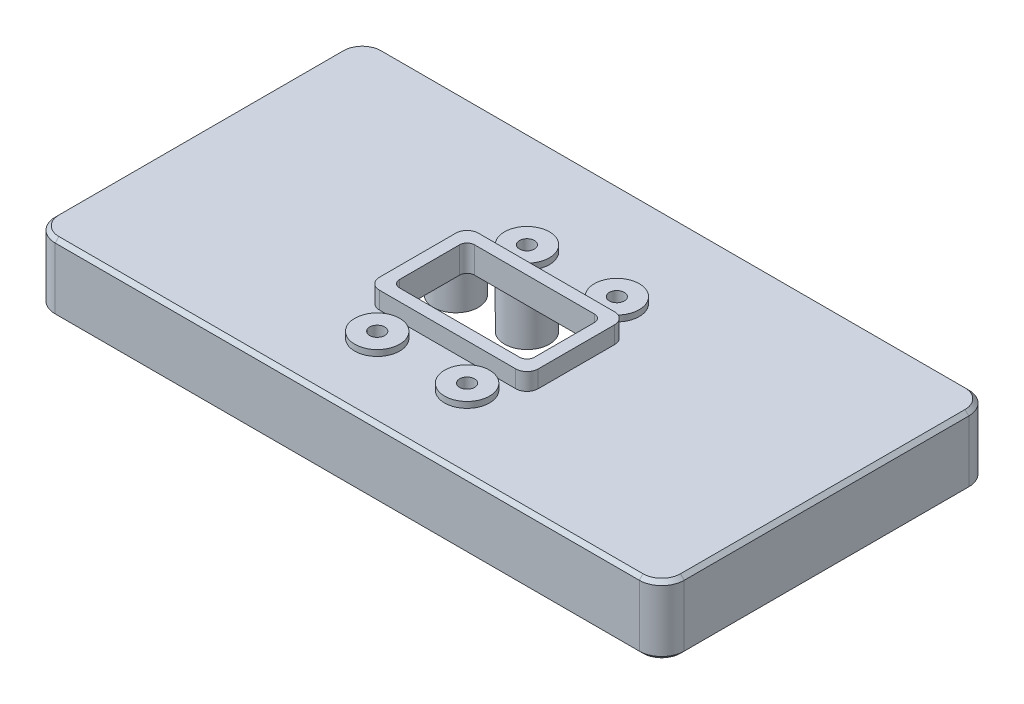
SolidWorks part; units mm, degrees
ref_plane "Front Plane" through (0, 0, 0) normal (0, 0, 1) x (1, 0, 0)
ref_plane "Top Plane" through (0, 0, 0) normal (0, 1, 0) x (1, 0, 0)
ref_plane "Right Plane" through (0, 0, 0) normal (1, 0, 0) x (0, 0, -1)
sketch "Sketch1" plane through (0, 0, 0) normal (0, 1, 0) x (1, 0, 0)
  line L0 (-39, -36) -> (39, -36)
  line L1 (42, -39) -> (42, -77)
  line L2 (39, -80) -> (-39, -80)
  line L3 (-42, -77) -> (-42, -39)
  arc A0 (-42, -39) -> (-39, -36) centre (-39, -39) cw
  arc A1 (39, -36) -> (42, -39) centre (39, -39) cw
  arc A2 (42, -77) -> (39, -80) centre (39, -77) cw
  arc A3 (-39, -80) -> (-42, -77) centre (-39, -77) cw
extrude "Boss-Extrude1" add sketch "Sketch1" along normal blind 9.2 from offset 50
chamfer "Chamfer1" distance 0.5 angle 45 8 edges at (0, 50, 36) (-41.1213, 50, 36.8787) (41.1213, 50, 36.8787) (-42, 50, 58) (42, 50, 58) (-41.1213, 50, 79.1213) (41.1213, 50, 79.1213) (0, 50, 80)
chamfer "Chamfer2" distance 0.5 angle 45 8 edges at (0, 59.2, 36) (-41.1213, 59.2, 36.8787) (41.1213, 59.2, 36.8787) (-42, 59.2, 58) (42, 59.2, 58) (-41.1213, 59.2, 79.1213) (41.1213, 59.2, 79.1213) (0, 59.2, 80)
sketch "Sketch2" plane through (0, 0, 0) normal (0, 1, 0) x (1, 0, 0)
  line L0 (-39, -37.6) -> (39, -37.6)
  line L1 (40.4, -39) -> (40.4, -77)
  line L2 (39, -78.4) -> (-39, -78.4)
  line L3 (-40.4, -77) -> (-40.4, -39)
  arc A0 (-40.4, -39) -> (-39, -37.6) centre (-39, -39) cw
  arc A1 (39, -37.6) -> (40.4, -39) centre (39, -39) cw
  arc A2 (40.4, -77) -> (39, -78.4) centre (39, -77) cw
  arc A3 (-39, -78.4) -> (-40.4, -77) centre (-39, -77) cw
extrude "Boss-Extrude2" add sketch "Sketch2" along normal blind 9 from offset 49 separate body
combine bodies "Combine1" operation type subtract main body 101 bodies to subtract 102
sketch "Sketch3" plane through (0, 0, 0) normal (0, 1, 0) x (1, 0, 0)
  circle A0 centre (-15, -50.5) radius 3
extrude "Boss-Extrude3" add sketch "Sketch3" along normal blind 8.01 from offset 50
sketch "Sketch4" plane through (0, 0, 0) normal (0, 1, 0) x (1, 0, 0)
  circle A0 centre (-15, -50.5) radius 1
extrude "Boss-Extrude4" add sketch "Sketch4" along normal blind 9.4 from offset 49 separate body
combine bodies "Combine2" operation type subtract main body 104 bodies to subtract 105
sketch "Sketch5" plane through (0, 0, 0) normal (0, 1, 0) x (1, 0, 0)
  circle A0 centre (-15, -69.5) radius 3
extrude "Boss-Extrude5" add sketch "Sketch5" along normal blind 8.01 from offset 50
sketch "Sketch6" plane through (0, 0, 0) normal (0, 1, 0) x (1, 0, 0)
  circle A0 centre (-15, -69.5) radius 1
extrude "Boss-Extrude6" add sketch "Sketch6" along normal blind 9.4 from offset 49 separate body
combine bodies "Combine3" operation type subtract main body 107 bodies to subtract 108
sketch "Sketch7" plane through (0, 0, 0) normal (0, 1, 0) x (1, 0, 0)
  circle A0 centre (15, -50.5) radius 3
extrude "Boss-Extrude7" add sketch "Sketch7" along normal blind 8.01 from offset 50
sketch "Sketch8" plane through (0, 0, 0) normal (0, 1, 0) x (1, 0, 0)
  circle A0 centre (15, -50.5) radius 1
extrude "Boss-Extrude8" add sketch "Sketch8" along normal blind 9.4 from offset 49 separate body
combine bodies "Combine4" operation type subtract main body 110 bodies to subtract 111
sketch "Sketch9" plane through (0, 0, 0) normal (0, 1, 0) x (1, 0, 0)
  circle A0 centre (15, -69.5) radius 3
extrude "Boss-Extrude9" add sketch "Sketch9" along normal blind 8.01 from offset 50
sketch "Sketch10" plane through (0, 0, 0) normal (0, 1, 0) x (1, 0, 0)
  circle A0 centre (15, -69.5) radius 1
extrude "Boss-Extrude10" add sketch "Sketch10" along normal blind 9.4 from offset 49 separate body
combine bodies "Combine5" operation type subtract main body 113 bodies to subtract 114
sketch "Sketch11" plane through (0, 0, 0) normal (0, 1, 0) x (1, 0, 0)
  circle A0 centre (-6, -50) radius 3
extrude "Boss-Extrude11" add sketch "Sketch11" along normal blind 10 from offset 50
sketch "Sketch12" plane through (0, 0, 0) normal (0, 1, 0) x (1, 0, 0)
  circle A0 centre (-6, -50) radius 1
extrude "Boss-Extrude12" add sketch "Sketch12" along normal blind 9.5 from offset 51.5 separate body
combine bodies "Combine6" operation type subtract main body 116 bodies to subtract 117
sketch "Sketch13" plane through (0, 0, 0) normal (0, 1, 0) x (1, 0, 0)
  circle A0 centre (-6, -70) radius 3
extrude "Boss-Extrude13" add sketch "Sketch13" along normal blind 10 from offset 50
sketch "Sketch14" plane through (0, 0, 0) normal (0, 1, 0) x (1, 0, 0)
  circle A0 centre (-6, -70) radius 1
extrude "Boss-Extrude14" add sketch "Sketch14" along normal blind 9.5 from offset 51.5 separate body
combine bodies "Combine7" operation type subtract main body 119 bodies to subtract 120
sketch "Sketch15" plane through (0, 0, 0) normal (0, 1, 0) x (1, 0, 0)
  circle A0 centre (6, -50) radius 3
extrude "Boss-Extrude15" add sketch "Sketch15" along normal blind 10 from offset 50
sketch "Sketch16" plane through (0, 0, 0) normal (0, 1, 0) x (1, 0, 0)
  circle A0 centre (6, -50) radius 1
extrude "Boss-Extrude16" add sketch "Sketch16" along normal blind 9.5 from offset 51.5 separate body
combine bodies "Combine8" operation type subtract main body 122 bodies to subtract 123
sketch "Sketch17" plane through (0, 0, 0) normal (0, 1, 0) x (1, 0, 0)
  circle A0 centre (6, -70) radius 3
extrude "Boss-Extrude17" add sketch "Sketch17" along normal blind 10 from offset 50
sketch "Sketch18" plane through (0, 0, 0) normal (0, 1, 0) x (1, 0, 0)
  circle A0 centre (6, -70) radius 1
extrude "Boss-Extrude18" add sketch "Sketch18" along normal blind 9.5 from offset 51.5 separate body
combine bodies "Combine9" operation type subtract main body 125 bodies to subtract 126
sketch "Sketch19" plane through (0, 0, 0) normal (0, 1, 0) x (1, 0, 0)
  line L0 (-38.99, -37.59) -> (38.99, -37.59)
  line L1 (40.39, -38.99) -> (40.39, -77.01)
  line L2 (38.99, -78.41) -> (-38.99, -78.41)
  line L3 (-40.39, -77.01) -> (-40.39, -38.99)
  line L4 (-33.6, -39.6) -> (33.6, -39.6)
  line L5 (34.6, -40.6) -> (34.6, -71.6)
  line L6 (33.6, -72.6) -> (-33.6, -72.6)
  line L7 (-34.6, -71.6) -> (-34.6, -40.6)
  arc A0 (-40.39, -38.99) -> (-38.99, -37.59) centre (-38.99, -38.99) cw
  arc A1 (38.99, -37.59) -> (40.39, -38.99) centre (38.99, -38.99) cw
  arc A2 (40.39, -77.01) -> (38.99, -78.41) centre (38.99, -77.01) cw
  arc A3 (-38.99, -78.41) -> (-40.39, -77.01) centre (-38.99, -77.01) cw
  arc A4 (-34.6, -40.6) -> (-33.6, -39.6) centre (-33.6, -40.6) cw
  arc A5 (33.6, -39.6) -> (34.6, -40.6) centre (33.6, -40.6) cw
  arc A6 (34.6, -71.6) -> (33.6, -72.6) centre (33.6, -71.6) cw
  arc A7 (-33.6, -72.6) -> (-34.6, -71.6) centre (-33.6, -71.6) cw
extrude "Boss-Extrude19" add sketch "Sketch19" along normal blind 1.2 from offset 50
sketch "Sketch20" plane through (0, 0, 0) normal (0, 1, 0) x (1, 0, 0)
  line L0 (-9.1, -53.4) -> (9.1, -53.4)
  line L1 (10.6, -54.9) -> (10.6, -65.1)
  line L2 (9.1, -66.6) -> (-9.1, -66.6)
  line L3 (-10.6, -65.1) -> (-10.6, -54.9)
  arc A0 (-10.6, -54.9) -> (-9.1, -53.4) centre (-9.1, -54.9) cw
  arc A1 (9.1, -53.4) -> (10.6, -54.9) centre (9.1, -54.9) cw
  arc A2 (10.6, -65.1) -> (9.1, -66.6) centre (9.1, -65.1) cw
  arc A3 (-9.1, -66.6) -> (-10.6, -65.1) centre (-9.1, -65.1) cw
extrude "Boss-Extrude20" add sketch "Sketch20" along normal blind 3.51 from offset 57.99
sketch "Sketch21" plane through (0, 0, 0) normal (0, 1, 0) x (1, 0, 0)
  line L0 (-8, -55) -> (8, -55)
  line L1 (9, -56) -> (9, -64)
  line L2 (8, -65) -> (-8, -65)
  line L3 (-9, -64) -> (-9, -56)
  arc A0 (-9, -56) -> (-8, -55) centre (-8, -56) cw
  arc A1 (8, -55) -> (9, -56) centre (8, -56) cw
  arc A2 (9, -64) -> (8, -65) centre (8, -64) cw
  arc A3 (-8, -65) -> (-9, -64) centre (-8, -64) cw
extrude "Boss-Extrude21" add sketch "Sketch21" along normal blind 13 from offset 49 separate body
combine bodies "Combine10" operation type subtract main body 129 bodies to subtract 130
